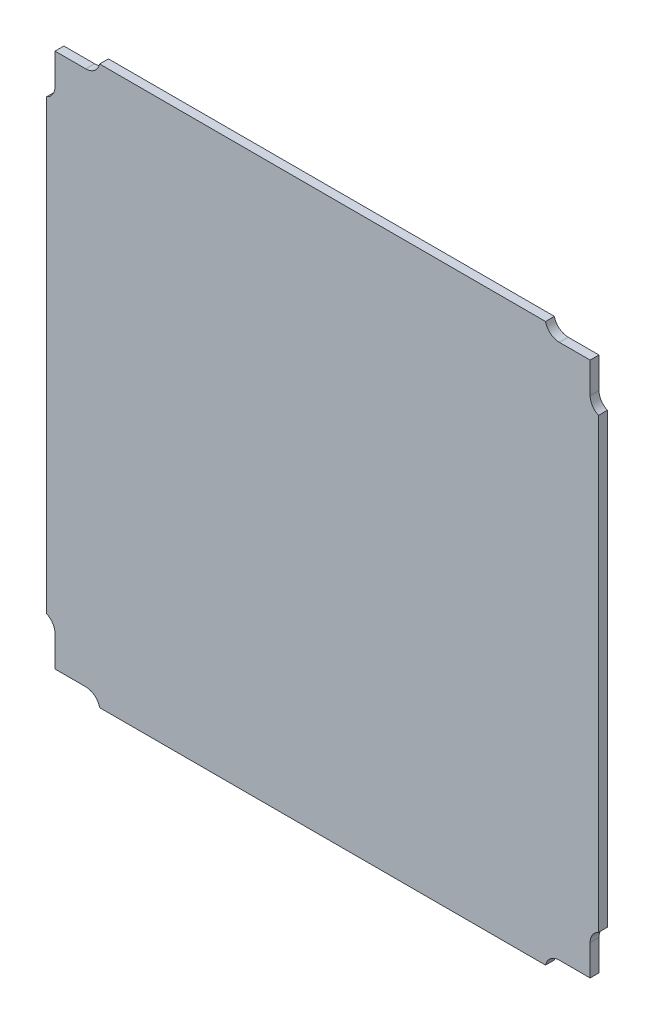
SolidWorks part; units mm, degrees
ref_plane "Front Plane" through (0, 0, 0) normal (0, 0, 1) x (1, 0, 0)
ref_plane "Top Plane" through (0, 0, 0) normal (0, 1, 0) x (1, 0, 0)
ref_plane "Right Plane" through (0, 0, 0) normal (1, 0, 0) x (0, 0, -1)
sketch "Sketch1" plane through (0, 0, 0) normal (0, 0, 1) x (1, 0, 0)
  line L0 (-40, 50) -> (-40, 48)
  line L1 (-50, -50) -> (50, -50)
  line L2 (-50, -50) -> (-50, 50)
  line L3 (-50, 50) -> (50, 50)
  line L4 (50, -50) -> (50, 50)
  line L5 (-50, -50) -> (50, 50) construction
  line L6 (-50, 50) -> (50, -50) construction
  line L7 (-50, 50) -> (-40, 50)
  line L8 (-50, 50) -> (-50, 40)
  line L9 (-40, 48) -> (-48, 48)
  line L10 (-48, 48) -> (-48, 40)
  line L11 (50, 50) -> (40, 50)
  line L12 (50, 50) -> (50, 40)
  line L13 (-48, 40) -> (-50, 40)
  line L14 (50, 40) -> (48, 40)
  line L15 (-50, -50) -> (-37.8649, -50)
  line L16 (-50, -50) -> (-50, -37.8649)
  line L17 (50, 50) -> (50, 40)
  line L18 (50, 50) -> (40, 50)
  line L19 (50, -50) -> (41.5, -50)
  line L20 (50, -50) -> (50, -41.5)
  line L21 (48, 40) -> (48, 48)
  line L22 (48, 48) -> (40, 48)
  line L23 (40, 48) -> (40, 50)
  line L24 (40, -50) -> (40, -48)
  line L25 (50, -50) -> (40, -50)
  line L26 (50, -50) -> (50, -40)
  line L27 (40, -48) -> (48, -48)
  line L28 (48, -48) -> (48, -40)
  line L29 (48, -40) -> (50, -40)
  line L30 (-50, -40) -> (-48, -40)
  line L31 (-50, -50) -> (-50, -40)
  line L32 (-50, -50) -> (-40, -50)
  line L33 (-48, -40) -> (-48, -48)
  line L34 (-48, -48) -> (-40, -48)
  line L35 (-40, -48) -> (-40, -50)
  point P0 (0, 0)
  point P38 (0, 0)
  dimension "D1" = 100
  dimension "D2" = 100
  dimension "D3" = 2
  dimension "D4" = 10
  dimension "D5" = 4
extrude "Boss-Extrude1" add sketch "Sketch1" along normal blind 1.5875 contours L1 L4 L3 L2 region at (0, 0, 0)
fillet "Fillet1" radius 2.54 8 edges at (-48, -40, 0.7937) (-40, -48, 0.7937) (40, -48, 0.7937) (48, -40, 0.7937) (48, 40, 0.7937) (40, 48, 0.7937) (-40, 48, 0.7937) (-48, 40, 0.7937)
sketch "Sketch6" plane through (0, 0, 1.5875) normal (0, 0, 1) x (1, 0, 0)
  line L0 (-40, 50) -> (40, 50) construction
  line L1 (-49.5, 50) -> (49.5, 50)
  line L2 (-49.5, 50) -> (-49.5, -50)
  line L3 (-49.5, -50) -> (49.5, -50)
  line L4 (49.5, 50) -> (49.5, -50)
  line L5 (-40, -50) -> (40, -50) construction
  line L6 (50, -40) -> (50, 40) construction
  dimension "D1" = 99
  dimension "D2" = 0.5
extrude "Cut-Extrude2" cut sketch "Sketch6" against normal through all flip side to cut
ref_axis "Axis1" through (0, 0, 0) along (0, 0, 1)
